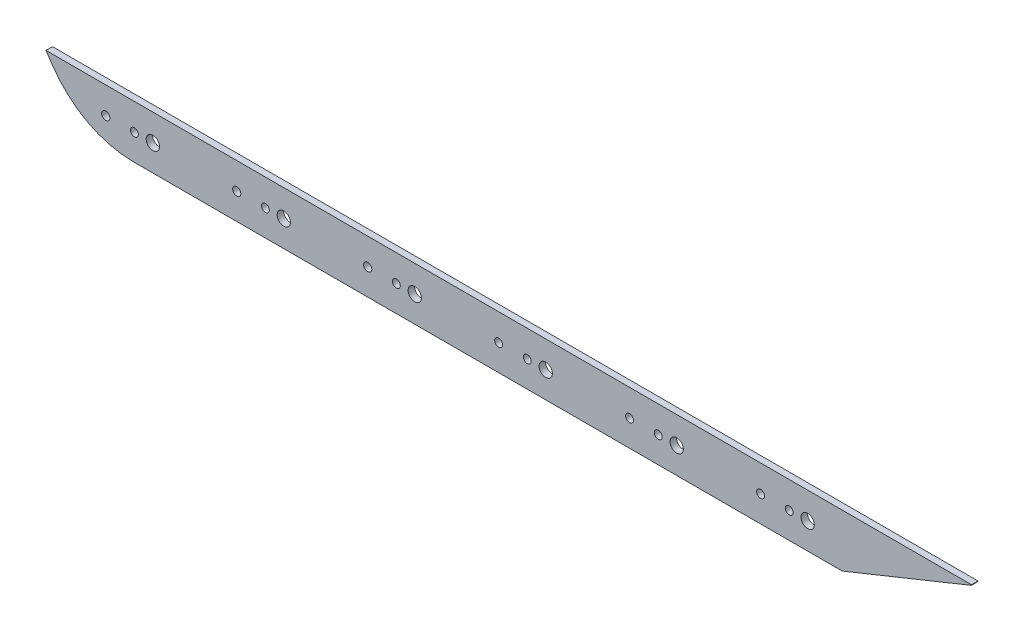
SolidWorks part; units mm, degrees
material "5052-H34"
ref_plane "Front Plane" through (0, 0, 0) normal (0, 0, 1) x (1, 0, 0)
ref_plane "Top Plane" through (0, 0, 0) normal (0, 1, 0) x (1, 0, 0)
ref_plane "Right Plane" through (0, 0, 0) normal (1, 0, 0) x (0, 0, -1)
sketch "Sketch1" plane through (0, 0, 0) normal (0, 0, 1) x (1, 0, 0)
  line L3 (428.1206, 28.9396) -> (0.5404, 28.9396)
  line L6 (-98.8794, 3.851) -> (-31.8794, -96.649)
  line L7 (428.1206, 28.9396) -> (403.1206, -71.149)
  line L9 (403.1206, -71.149) -> (366, -96.649)
  line L10 (-31.8794, -96.649) -> (366, -96.649)
  line L11 (0.5404, 28.9396) -> (-115.6052, 28.9396)
  line L12 (-98.8794, 3.851) -> (-115.6052, 28.9396)
  line L13 (-49.0861, -70.839) -> (403.198, -70.839)
  circle A0 centre (3.1206, -83.899) radius 3.25
  circle A1 centre (67.1206, -83.899) radius 3.25
  circle A2 centre (131.1206, -83.899) radius 3.25
  circle A3 centre (195.1206, -83.899) radius 3.25
  circle A4 centre (259.1206, -83.899) radius 3.25
  circle A5 centre (323.1206, -83.899) radius 3.25
  point P0 (-48.8794, -71.149)
  point P2 (-31.8794, -96.649)
  point P8 (48, -83.899)
  point P9 (403.1206, -71.149)
  point P23 (-49.0861, -70.839)
  point P25 (403.198, -70.839)
  dimension "D2" = 64
  dimension "D4" = 64
  dimension "D1" = 25.5
  dimension "D3" = 75
  dimension "D5" = 25
  dimension "D6" = 80
  dimension "D7" = 527
  dimension "D8" = 180
  dimension "D9" = 64
  dimension "D10" = 64
  dimension "D11" = 64
  dimension "D12" = 123.69
  dimension "D13" = 12.75
  dimension "D14" = 25.81
  dimension "D15" = 25.81
extrude "Boss-Extrude1" add sketch "Sketch1" along normal blind 3.175 contours L3 L11 L12 L6 L10 L9 L7
extrude "Cut-Extrude1" cut sketch "Sketch1<4>" along normal through all contours A0 | A1 | A2 | A3 | A4 | A5 region at (3.1206, -83.899, 0)
sketch "Sketch1<4>" plane through (0, 0, 0) normal (0, 0, 1) x (1, 0, 0) same geometry as "Sketch1"
sketch "Sketch5" plane through (0, 0, 0) normal (0, 0, -1) x (-1, 0, 0)
  line L0 (48.8794, -71.149) -> (-14.2353, -96.649)
  line L1 (31.8794, -96.649) -> (-366, -96.649) construction
  line L2 (-14.2353, -96.649) -> (31.8794, -96.649)
  line L3 (31.8794, -96.649) -> (48.8794, -71.149)
  line L6 (-366, -96.649) -> (-403.1206, -71.149)
  line L7 (-403.1206, -71.149) -> (-352, -71.149)
  line L9 (-352, -71.149) -> (-326.5, -96.649)
  line L11 (-366, -96.649) -> (-326.5, -96.649)
  dimension "D1" = 22
  dimension "D2" = 45
extrude "Cut-Extrude2" [suppressed] cut sketch "Sketch5" against normal up to next
fillet "Fillet1" radius 48 1 edges at (-31.8794, -96.649, 1.5875)
sketch "Sketch7" plane through (0, 0, 3.175) normal (0, 0, 1) x (1, 0, 0)
  line L0 (403.1206, -71.149) -> (340.0059, -96.649)
  line L1 (-31.8794, -96.649) -> (366, -96.649) construction
  line L2 (340.0059, -96.649) -> (366, -96.649)
  line L3 (366, -96.649) -> (403.1206, -71.149)
  dimension "D1" = 22
extrude "Cut-Extrude3" cut sketch "Sketch7" against normal blind 10
sketch "Sketch9" plane through (0, 0, 0) normal (0, 0, -1) x (-1, 0, 0)
  line L0 (-403.1206, -71.149) -> (48.8794, -71.149)
  line L1 (48.8794, -71.149) -> (48.8794, -114.9143)
  line L2 (48.8794, -114.9143) -> (-403.1206, -114.9143)
  line L3 (-403.1206, -114.9143) -> (-403.1206, -71.149)
extrude "Cut-Extrude4" [suppressed] cut sketch "Sketch9" against normal blind 10
sketch "Sketch11" plane through (0, 0, 3.175) normal (0, 0, 1) x (1, 0, 0)
  line L0 (-49.0861, -70.839) -> (403.198, -70.839) construction
  line L1 (-49.0861, -70.839) -> (403.198, -70.839)
  line L3 (-115.6052, 28.9396) -> (428.1206, 28.9396)
  line L4 (428.1206, 28.9396) -> (403.198, -70.839)
  line L5 (-49.0861, -70.839) -> (-115.6052, 28.9396)
extrude "Cut-Extrude5" cut sketch "Sketch11" against normal blind 10
sketch "Sketch13" plane through (0, 0, 0) normal (0, 0, -1) x (-1, 0, 0)
  circle A0 centre (-58.1206, -83.8863) radius 1.925
  circle A1 centre (-44.1206, -83.8863) radius 2
  circle A2 centre (5.8794, -83.8863) radius 1.925
  circle A3 centre (19.8794, -83.8863) radius 2
  circle A6 centre (-122.1206, -83.899) radius 1.925
  circle A7 centre (-108.1206, -83.899) radius 2
  circle A8 centre (-186.1206, -83.899) radius 1.925
  circle A9 centre (-172.1206, -83.899) radius 1.925
  circle A10 centre (-250.1206, -83.899) radius 1.925
  circle A11 centre (-236.1206, -83.899) radius 1.925
  circle A12 centre (-314.1206, -83.899) radius 1.925
  circle A13 centre (-300.1206, -83.899) radius 1.925
  dimension "D1" = 9
  dimension "D2" = 4
  dimension "D7" = 3.85
  dimension "D8" = 4
  dimension "D9" = 14
  dimension "D3" = 9
  dimension "D4" = 9
  dimension "D5" = 14
  dimension "D6" = 14
  dimension "D10" = 9
  dimension "D11" = 14
  dimension "D12" = 9
  dimension "D13" = 14
  dimension "D14" = 9
  dimension "D15" = 14
extrude "Cut-Extrude6" cut sketch "Sketch13" against normal blind 10
